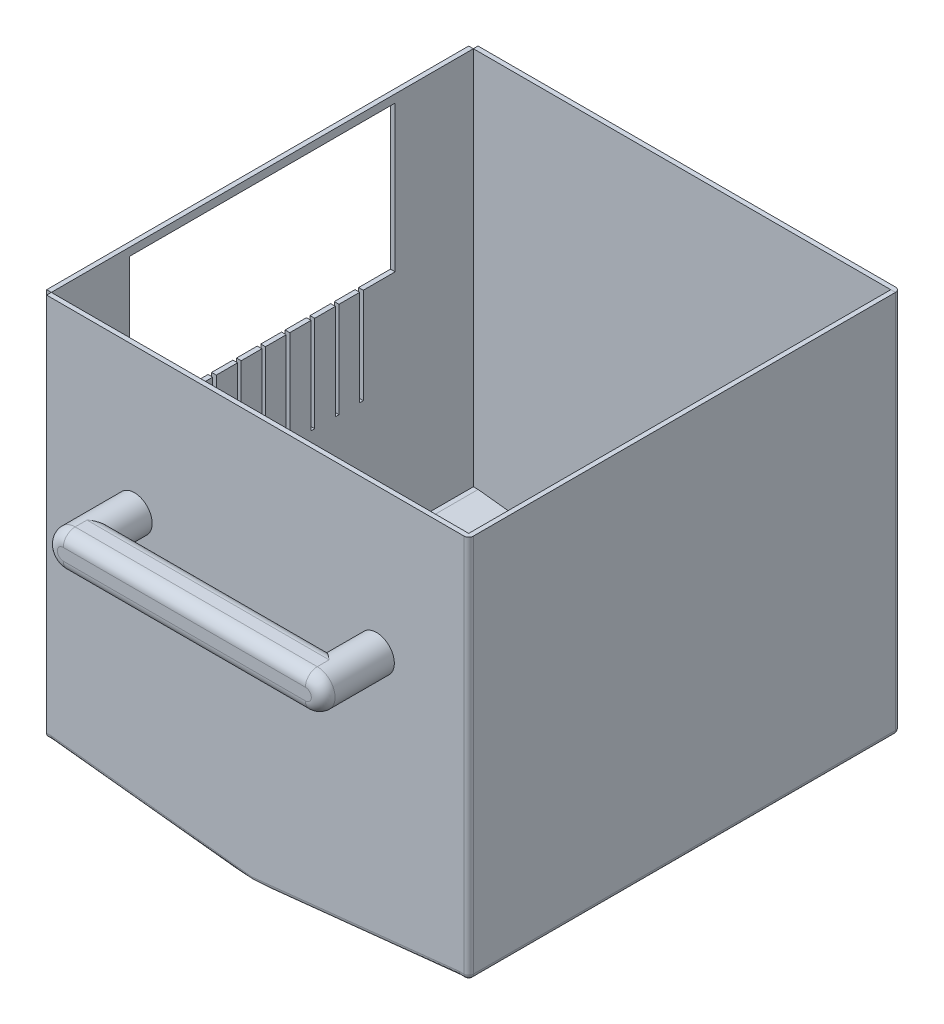
SolidWorks part; units mm, degrees
ref_plane "Front Plane" through (0, 0, 0) normal (0, 0, 1) x (1, 0, 0)
ref_plane "Top Plane" through (0, 0, 0) normal (0, 1, 0) x (1, 0, 0)
ref_plane "Right Plane" through (0, 0, 0) normal (1, 0, 0) x (0, 0, -1)
sketch "Sketch1" plane through (0, 0, 0) normal (0, 1, 0) x (1, 0, 0)
  line L1 (-366.5236, 350.2973) -> (547.8764, 350.2973)
  line L2 (-366.5236, 350.2973) -> (-366.5236, -564.1027)
  line L3 (-366.5236, -564.1027) -> (547.8764, -564.1027)
  line L4 (547.8764, 350.2973) -> (547.8764, -564.1027)
  dimension "D1" = 914.4
  dimension "D2" = 914.4
extrude "Boss-Extrude1" add sketch "Sketch1" along normal blind 50
sketch "Sketch2" plane through (547.8764, 0, 0) normal (1, 0, 0) x (0, 0, -1)
  line L0 (350.2973, 50) -> (350.2973, 0) construction
  line L1 (-564.1027, 0) -> (350.2973, 0)
  line L2 (-564.1027, 0) -> (-564.1027, 883.92)
  line L3 (-564.1027, 883.92) -> (350.2973, 883.92)
  line L4 (350.2973, 0) -> (350.2973, 883.92)
  dimension "D1" = 0
  dimension "D2" = 883.92
extrude "Boss-Extrude2" add sketch "Sketch2" against normal blind 10
sketch "Sketch3" plane through (-366.5236, 0, 0) normal (-1, 0, 0) x (0, 0, 1)
  line L1 (-350.2973, 0) -> (564.1027, 0)
  line L2 (-350.2973, 0) -> (-350.2973, 883.92)
  line L3 (-350.2973, 883.92) -> (564.1027, 883.92)
  line L4 (564.1027, 0) -> (564.1027, 883.92)
extrude "Boss-Extrude3" add sketch "Sketch3" against normal blind 10
sketch "Sketch5" plane through (0, 0, 564.1027) normal (0, 0, 1) x (1, 0, 0)
  line L1 (-366.5236, 0) -> (547.8764, 0)
  line L2 (-366.5236, 0) -> (-366.5236, 883.92)
  line L3 (-366.5236, 883.92) -> (547.8764, 883.92)
  line L4 (547.8764, 0) -> (547.8764, 883.92)
extrude "Boss-Extrude4" add sketch "Sketch5" against normal blind 10
sketch "Sketch10" plane through (0, 0, -350.2973) normal (0, 0, -1) x (-1, 0, 0)
  line L0 (-74.2018, 0) -> (-149.6109, 0)
  line L1 (-74.2018, 0) -> (-19.3472, 0)
  line L2 (-19.3472, 0) -> (346.393, 40)
  line L3 (346.393, 40) -> (381.7156, 40)
  line L6 (-149.6109, 0) -> (-527.8764, 40)
  line L7 (-527.8764, 40) -> (-547.8764, 40)
  line L10 (381.7156, 40) -> (381.7156, 0)
  line L11 (381.7156, 0) -> (-19.3472, 0)
  line L12 (-547.8764, 40) -> (-547.8764, 0)
  line L13 (-547.8764, 0) -> (-149.6109, 0)
  line L14 (-527.8764, 50) -> (-149.6109, 9.2201)
  line L15 (-149.6109, 9.2201) -> (-149.6109, 0)
  line L16 (-527.8764, 50) -> (346.393, 50)
  line L17 (346.393, 50) -> (-19.3472, 9.2201)
  line L18 (-537.8764, 50) -> (-527.8764, 50)
  line L19 (-19.3472, 9.2201) -> (-149.6109, 9.2201)
  line L20 (-19.3472, 0) -> (-19.3472, 9.2201)
  line L21 (346.393, 40) -> (346.393, 50)
  line L22 (346.393, 50) -> (356.393, 50)
  line L23 (-547.8764, 0) -> (366.5236, 0) construction
  line L24 (-547.8764, 883.92) -> (-547.8764, 0) construction
  line M18 (-547.8764, 0) -> (366.5236, 0)
  line M19 (366.5236, 0) -> (366.5236, 883.92)
  line M22 (356.5236, 50) -> (-537.8764, 50)
  line M25 (-547.8764, 883.92) -> (-547.8764, 0)
  dimension "D1" = 35.3226
  dimension "D2" = 378.2656
  dimension "D3" = 378.2656
  dimension "D4" = 9.2201
  dimension "D5" = 0.117
  dimension "D6" = 130.2636
  dimension "D7" = 6.153
  dimension "D8" = 6.362
  dimension "D9" = 40.7799
  dimension "D10" = 0
extrude "Cut-Extrude1" cut sketch "Sketch10" against normal through all both and the other way through all contours L6 L7 M25 M18 | L3 L2 M18 M19 region at (414.8024, 13.9709, -350.2973) region at (-237.5673, 13.9944, -350.2973)
extrude "Cut-Extrude2" cut sketch "Sketch10<3>" against normal blind 904.4 contours L19 L17 L14 M22 region at (88.3834, 34.644, -350.2973)
sketch "Sketch10<3>" plane through (0, 0, -350.2973) normal (0, 0, -1) x (-1, 0, 0) same geometry as "Sketch10"
sketch "Sketch11" plane through (0, 0, -350.2973) normal (0, 0, -1) x (-1, 0, 0)
  line L0 (-537.8764, 883.92) -> (356.5236, 883.92)
  line L1 (356.5236, 50) -> (356.5236, 883.92) construction
  line L2 (-537.8764, 883.92) -> (356.5236, 883.92) construction
  line L10 (-537.8764, 883.92) -> (-547.8764, 883.92)
  line L11 (-547.8764, 883.92) -> (-547.8764, 50)
  line L12 (-547.8764, 883.92) -> (-547.8764, 40) construction
  line L14 (356.5236, 883.92) -> (366.5236, 883.92)
  line L15 (366.5236, 883.92) -> (366.5236, 50)
  line L16 (366.5236, 883.92) -> (366.5236, 40) construction
  line L18 (366.5236, 50) -> (366.5236, 40)
  line L19 (366.5236, 40) -> (346.393, 40) construction
  line L20 (366.5236, 40) -> (346.393, 40)
  line L21 (346.393, 40) -> (-19.3472, 0)
  line L22 (-19.3472, 0) -> (-149.6109, 0)
  line L23 (-149.6109, 0) -> (-527.8764, 40)
  line L24 (-527.8764, 40) -> (-547.8764, 40)
  line L25 (-547.8764, 40) -> (-547.8764, 50)
extrude "Boss-Extrude5" add sketch "Sketch11" along normal blind 10 separate body
fillet "Fillet1" radius 10 2 edges at (547.8764, 461.96, 564.1027) (-366.5236, 461.96, 564.1027)
fillet "Fillet2" radius 10 9 edges at (-366.5236, 40, 101.9027) (-363.5947, 40, 561.1738) (-351.4583, 40, 564.1027) (532.8764, 40, 564.1027) (544.9475, 40, 561.1738) (547.8764, 40, 101.9027) (-346.393, 40, 106.9027) (-163.5229, 20, 564.1027) (338.7436, 20, 564.1027)
fillet "Fillet3" radius 10 6 edges at (547.8764, 461.96, -360.2973) (-366.5236, 461.96, -360.2973) (-356.4583, 40, -360.2973) (-163.5229, 20, -360.2973) (537.8764, 40, -360.2973) (338.7436, 20, -360.2973)
sketch "Sketch14" plane through (-366.5236, 0, 0) normal (-1, 0, 0) x (0, 0, 1)
  line L0 (-350.2973, 883.92) -> (-350.2973, 50) construction
  line L1 (-182.6573, 532.6) -> (386.4627, 532.6)
  line L2 (-182.6573, 532.6) -> (-182.6573, 845.82)
  line L3 (-182.6573, 845.82) -> (386.4627, 845.82)
  line L4 (386.4627, 532.6) -> (386.4627, 845.82)
  line L5 (554.1027, 50) -> (554.1027, 883.92) construction
  line L6 (-350.2973, 50) -> (554.1027, 50) construction
  line L7 (554.1027, 883.92) -> (-350.2973, 883.92) construction
  dimension "D1" = 167.64
  dimension "D2" = 167.64
  dimension "D3" = 482.6
  dimension "D4" = 38.1
extrude "Cut-Extrude4" cut sketch "Sketch14" against normal blind 10
sketch "Sketch15" plane through (0, 0, -360.2973) normal (0, 0, -1) x (-1, 0, 0)
  line L0 (366.5236, 50) -> (366.5236, 883.92) construction
  line L1 (-547.8764, 883.92) -> (366.5236, 883.92)
  line L2 (-547.8764, 883.92) -> (-547.8764, 862.838)
  line L3 (-547.8764, 862.838) -> (366.5236, 862.838)
  line L4 (366.5236, 883.92) -> (366.5236, 862.838)
  dimension "D1" = 21.082
extrude "Cut-Extrude5" cut sketch "Sketch15" against normal through all
sketch "Sketch16" plane through (0, 0, 564.1027) normal (0, 0, 1) x (1, 0, 0)
  circle A0 centre (-168.4324, 552.1316) radius 38.1
  circle A1 centre (350.4081, 552.1316) radius 38.1
  dimension "D1" = 76.2
  dimension "D2" = 76.2
extrude "Boss-Extrude6" add sketch "Sketch16" along normal blind 76.2
sketch "Sketch17" plane through (0, 0, 640.3027) normal (0, 0, 1) x (1, 0, 0)
  line L0 (-168.4324, 590.2316) -> (350.4081, 590.2316)
  line L1 (-168.4324, 514.0316) -> (350.4081, 514.0316)
  circle A0 centre (-168.4324, 552.1316) radius 38.1 construction
  circle A1 centre (-168.4324, 552.1316) radius 38.1 construction
  circle A2 centre (350.4081, 552.1316) radius 38.1 construction
  circle A3 centre (350.4081, 552.1316) radius 38.1 construction
  arc A4 (-168.4324, 514.0316) -> (-168.4324, 590.2316) centre (-168.4324, 552.1316) cw
  arc A5 (350.4081, 590.2316) -> (350.4081, 514.0316) centre (350.4081, 552.1316) cw
extrude "Boss-Extrude7" add sketch "Sketch17" along normal blind 76.2
fillet "Fillet4" radius 25.4 4 edges at (388.5081, 552.1316, 716.5027) (90.9878, 514.0316, 716.5027) (-206.5324, 552.1316, 716.5027) (90.9878, 590.2316, 716.5027)
fillet "Fillet5" radius 25.4 2 edges at (90.9878, 514.0316, 640.3027) (90.9878, 590.2316, 640.3027)
sketch "Sketch18" plane through (-366.5236, 0, 0) normal (-1, 0, 0) x (0, 0, 1)
  line L0 (-62.3171, 530.8) -> (-62.3171, 327.6) construction
  line L1 (-114.3871, 532.6) -> (-106.7671, 532.6)
  line L2 (-114.3871, 532.6) -> (-114.3871, 327.6)
  line L3 (-114.3871, 327.6) -> (-106.7671, 327.6)
  line L4 (554.1027, 50) -> (554.1027, 862.838)
  line L5 (554.1027, 862.838) -> (-350.2973, 862.838)
  line L6 (-350.2973, 862.838) -> (-350.2973, 50)
  line L7 (-350.2973, 50) -> (554.1027, 50)
  line L8 (554.1027, 50) -> (554.1027, 862.838)
  line L9 (554.1027, 862.838) -> (-350.2973, 862.838)
  line L10 (-350.2973, 862.838) -> (-350.2973, 50)
  line L11 (-350.2973, 50) -> (554.1027, 50)
  line L12 (-106.7671, 532.6) -> (-106.7671, 327.6)
  line L13 (-62.3171, 532.6) -> (-54.6971, 532.6)
  line L14 (-62.3171, 532.6) -> (-62.3171, 327.6)
  line L15 (-62.3171, 327.6) -> (-54.6971, 327.6)
  line L16 (-54.6971, 532.6) -> (-54.6971, 327.6)
  line L19 (-10.2471, 327.6) -> (-2.6271, 327.6)
  line L20 (-10.2471, 327.6) -> (-10.2471, 532.6)
  line L21 (-10.2471, 532.6) -> (-2.6271, 532.6)
  line L22 (-2.6271, 327.6) -> (-2.6271, 532.6)
  line L23 (50.7129, 532.6) -> (43.0929, 532.6)
  line L24 (50.7129, 532.6) -> (50.7129, 327.6)
  line L25 (50.7129, 327.6) -> (43.0929, 327.6)
  line L26 (43.0929, 532.6) -> (43.0929, 327.6)
  line L27 (95.1629, 532.6) -> (102.7829, 532.6)
  line L28 (95.1629, 532.6) -> (95.1629, 327.6)
  line L29 (95.1629, 327.6) -> (102.7829, 327.6)
  line L30 (102.7829, 532.6) -> (102.7829, 327.6)
  line L31 (147.2329, 532.6) -> (154.8529, 532.6)
  line L32 (147.2329, 532.6) -> (147.2329, 327.6)
  line L33 (147.2329, 327.6) -> (154.8529, 327.6)
  line L34 (154.8529, 532.6) -> (154.8529, 327.6)
  line L35 (200.5729, 532.6) -> (208.1929, 532.6)
  line L36 (200.5729, 532.6) -> (200.5729, 330.4426)
  line L37 (200.5729, 330.4426) -> (208.1929, 330.4426)
  line L38 (208.1929, 532.6) -> (208.1929, 330.4426)
  line L39 (252.6429, 532.6) -> (260.2629, 532.6)
  line L40 (252.6429, 532.6) -> (252.6429, 327.6)
  line L41 (252.6429, 327.6) -> (260.2629, 327.6)
  line L42 (260.2629, 532.6) -> (260.2629, 327.6)
  line L43 (304.7129, 327.6) -> (312.3329, 327.6)
  line L44 (304.7129, 327.6) -> (304.7129, 532.6)
  line L45 (304.7129, 532.6) -> (312.3329, 532.6)
  line L46 (312.3329, 327.6) -> (312.3329, 532.6)
  line L47 (-182.6573, 532.6) -> (386.4627, 532.6) construction
  dimension "D1" = 0
extrude "Cut-Extrude7" cut sketch "Sketch18" against normal up to surface (10 mm away) flip side to cut up to face at (-356.5236, 456.419, 101.9027)
